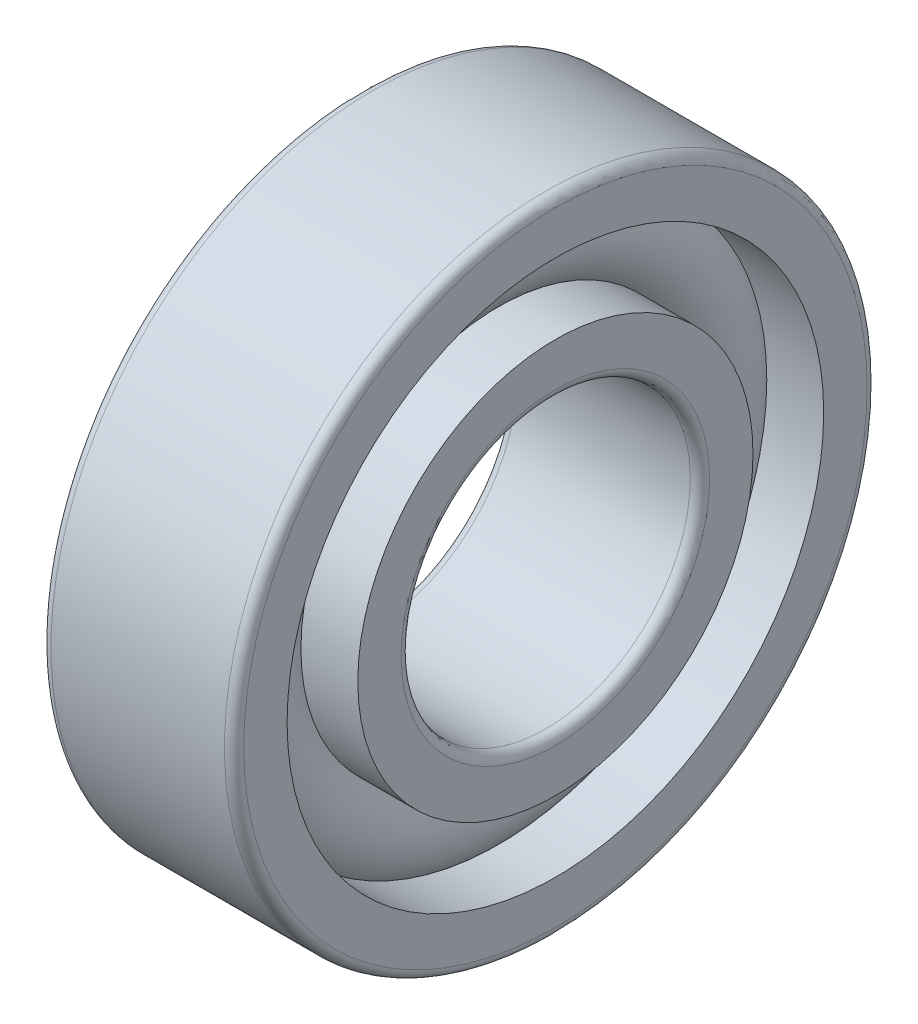
SolidWorks part; units mm, degrees
ref_plane "Plane1" through (0, 0, 0) normal (0, 0, 1) x (1, 0, 0)
ref_plane "Plane2" through (0, 0, 0) normal (0, 1, 0) x (1, 0, 0)
ref_plane "Plane3" through (0, 0, 0) normal (1, 0, 0) x (0, 0, -1)
sketch "Clipboard" plane through (0, 0, 0) normal (0, 0, 1) x (1, 0, 0)
  line L0 (-10, 0) -> (10, 0) construction
  line L1 (0, 0) -> (22.3471, -0.7804)
  line L2 (0, 0) -> (7.2456, 0.253)
  line L3 (0, 0) -> (22.3471, -0.7804)
  line L4 (0, 0) -> (-22.3573, -0.3902)
  dimension "BallCLRad" = 7.25
sketch "CagSpiSke" plane through (0, 0, 0) normal (0, 0, 1) x (1, 0, 0)
  line L0 (0.165, 6.975) -> (0.165, 7.525)
  line L1 (0.165, 7.525) -> (-0.165, 7.525)
  line L2 (-0.165, 7.525) -> (-0.165, 6.975)
  line L3 (-0.165, 6.975) -> (0.165, 6.975)
  line L4 (-20.6375, 0) -> (20.6375, 0) construction
  line L5 (0, 0) -> (0, 23.7692) construction
  dimension "OD" = 15.05
  dimension "ID" = 13.95
revolve "CageSpine" add sketch "CagSpiSke" angle 0.001 about L4
ref_axis "Axis1" through (-50, 0, 0) along (1, 0, 0)
sketch "CagBalSke" plane through (0, 0, 0) normal (0, 0, 1) x (1, 0, 0)
  line L0 (-1.815, 7.25) -> (1.815, 7.25)
  line L1 (-1.905, 7.25) -> (1.905, 7.25) construction
  line L2 (-10, 0) -> (10, 0) construction
  line L3 (0, 0) -> (0, 24) construction
  arc A0 (1.815, 7.25) -> (-1.815, 7.25) centre (0, 7.25) cw
  dimension "BallCLRad" = 7.25
revolve "CageBall" [suppressed] add sketch "CagBalSke" angle 360 about L1 reverse direction yes
pattern_circular "CageBalls" [suppressed] count 2 every 180 about axis through (-50, 0, 0) along (1, 0, 0)
sketch "CagTrmODSke" plane through (0, 0, 0) normal (0, 0, 1) x (1, 0, 0)
  line L0 (1.816, 7.525) -> (1.816, 9.066)
  line L1 (1.816, 9.066) -> (-1.816, 9.066)
  line L2 (-1.816, 9.066) -> (-1.816, 7.525)
  line L3 (-1.816, 7.525) -> (1.816, 7.525)
  line L4 (-20.6375, 0) -> (20.6375, 0) construction
  line L5 (0, 0) -> (0, 25) construction
  dimension "Width" = 3.632
  dimension "ID" = 15.05
  dimension "OD" = 18.132
revolve "CageTrimOD" [suppressed] cut sketch "CagTrmODSke" angle 360 about L4 reverse direction yes
sketch "CagTrmIDSke" plane through (0, 0, 0) normal (0, 0, 1) x (1, 0, 0)
  line L0 (1.816, 5.436) -> (1.816, 6.975)
  line L1 (1.816, 6.975) -> (-1.816, 6.975)
  line L2 (-1.816, 6.975) -> (-1.816, 5.436)
  line L3 (-1.816, 5.436) -> (1.816, 5.436)
  line L4 (-20.6375, 0) -> (20.6375, 0) construction
  line L5 (0, 0) -> (0, 25) construction
  dimension "Width" = 3.632
  dimension "ID" = 10.872
  dimension "OD" = 13.95
revolve "CageTrimID" [suppressed] cut sketch "CagTrmIDSke" angle 360 about L4 reverse direction yes
sketch "BalSimSke" plane through (0, 0, 0) normal (0, 0, 1) x (1, 0, 0)
  line L0 (-10, 0) -> (10, 0) construction
  line L1 (-10, 7.25) -> (10, 7.25) construction
  line L2 (0, 0) -> (0, 23) construction
  circle A0 centre (0, 7.25) radius 1.65
  dimension "BallCLRad" = 7.25
  dimension "Ball_diameter" = 3.3
revolve "BallsSimplified" add sketch "BalSimSke" angle 360 about L0
sketch "BalDetSke" plane through (0, 0, 0) normal (0, 0, 1) x (1, 0, 0)
  line L0 (-1.65, 7.25) -> (1.65, 7.25)
  line L1 (-1.905, 7.25) -> (1.905, 7.25) construction
  line L2 (0, 0) -> (0, 25) construction
  arc A0 (1.65, 7.25) -> (-1.65, 7.25) centre (0, 7.25) cw
  dimension "BallCLRad" = 7.25
  dimension "Ball_diameter" = 3.3
revolve "BallDetailed" [suppressed] add sketch "BalDetSke" angle 360 about L1 reverse direction yes
sketch "InnRacSke" plane through (0, 0, 0) normal (0, 0, 1) x (1, 0, 0)
  line L0 (-1.1961, 6.15) -> (-3, 6.15)
  line L1 (-3, 6.15) -> (-3, 4.8)
  line L2 (-2.7, 4.5) -> (2.7, 4.5)
  line L3 (3, 4.8) -> (3, 6.15)
  line L4 (3, 6.15) -> (1.1961, 6.15)
  line L5 (-20.6375, 0) -> (20.6375, 0) construction
  line L6 (0, 0) -> (0, 30) construction
  arc A0 (-3, 4.8) -> (-2.7, 4.5) centre (-2.7, 4.8) ccw
  arc A1 (2.7, 4.5) -> (3, 4.8) centre (2.7, 4.8) ccw
  arc A2 (1.1961, 6.15) -> (-1.1961, 6.15) centre (0, 7.25) cw
  dimension "BallCLRad" = 7.25
  dimension "Fillet_radius" = 0.3
  dimension "Ball_diameter" = 3.25
  dimension "ID" = 9
  dimension "OD" = 12.3
  dimension "Width" = 6
revolve "InnerRace" add sketch "InnRacSke" angle 360 about L5 reverse direction yes
sketch "OutRacSke" plane through (0, 0, 0) normal (0, 0, 1) x (1, 0, 0)
  line L0 (-1.1961, 8.35) -> (-3, 8.35)
  line L1 (-3, 8.35) -> (-3, 9.7)
  line L2 (-2.7, 10) -> (2.7, 10)
  line L3 (3, 9.7) -> (3, 8.35)
  line L4 (3, 8.35) -> (1.1961, 8.35)
  line L5 (-20.6375, 0) -> (20.6375, 0) construction
  line L6 (0, 0) -> (0, 30) construction
  arc A0 (-3, 9.7) -> (-2.7, 10) centre (-2.7, 9.7) cw
  arc A1 (2.7, 10) -> (3, 9.7) centre (2.7, 9.7) cw
  arc A2 (1.1961, 8.35) -> (-1.1961, 8.35) centre (0, 7.25) ccw
  dimension "BallCLRad" = 7.25
  dimension "Fillet_radius" = 0.3
  dimension "Ball_diameter" = 3.25
  dimension "Width" = 6
revolve "OuterRace" add sketch "OutRacSke" angle 360 about L5 reverse direction yes
pattern_circular "BallsDetailed" [suppressed] count 2 every 180 about axis through (-50, 0, 0) along (1, 0, 0)
equation "\"BallCLRad@Clipboard\" = ( \"OD@OutRacSke\" + \"ID@InnRacSke\" ) / 4"
equation "\"BallCLRad@BalSimSke\" = \"BallCLRad@Clipboard\""
equation "\"BallCLRad@BalDetSke\" = \"BallCLRad@Clipboard\""
equation "\"BallCLRad@InnRacSke\" = \"BallCLRad@Clipboard\""
equation "\"BallCLRad@OutRacSke\" = \"BallCLRad@Clipboard\""
equation "\"Ball_diameter@InnRacSke\" = \"Ball_diameter@BalDetSke\" - 0.05"
equation "\"Ball_diameter@OutRacSke\" = \"Ball_diameter@BalDetSke\" - 0.05"
equation "\"Ball_diameter@BalSimSke\" = \"Ball_diameter@BalDetSke\""
equation "\"Width@OutRacSke\" = \"Width@InnRacSke\""
equation "\"Fillet_radius@OutRacSke\" = \"Fillet_radius@InnRacSke\""
equation "\"Max_count@Clipboard\" = int( 3.14159265 / atn(( \"Ball_diameter@BalDetSke\" / 2) / sqr( \"BallCLRad@Clipboard\"  *  \"BallCLRad@Clipboard\" - ( \"Ball_diameter@BalDetSke\" / 2) *  ( \"Ball_diameter@BalDetSke\" / 2))))"
equation "\"Max_count@Clipboard\" = ((sgn( \"Max_count@Clipboard\" - \"Count@Clipboard\" )-1)*( \"Max_count@Clipboard\" - \"Count@Clipboard\" ))/-2+ \"Count@Clipboard\""
equation "\"Count@BallsDetailed\" = int( \"Show_count@Clipboard\" ) "
equation "\"Count@BallsDetailed\" = ((sgn( \"Count@BallsDetailed\" - \"Max_count@Clipboard\" )-1)*( \"Count@BallsDetailed\" - \"Max_count@Clipboard\" ))/-2+ \"Max_count@Clipboard\""
equation "\"Count@BallsDetailed\" = ((sgn( \"Count@BallsDetailed\" - \"Min_count@Clipboard\" )+1)*( \"Count@BallsDetailed\" - \"Min_count@Clipboard\"))/2 +\"Min_count@Clipboard\""
equation "\"Angle@BallsDetailed\" = 360.0 / \"Max_count@Clipboard\""
equation "\"BallCLRad@CagBalSke\" = \"BallCLRad@Clipboard\""
equation "\"Count@CageBalls\" = \"Count@BallsDetailed\""
equation "\"Angle@CageBalls\" = \"Angle@BallsDetailed\""
equation "\"Angle@CageSpine\" =  \"Angle@CageBalls\" * ( \"Count@CageBalls\" -1 + int( \"Count@CageBalls\" / \"Max_count@Clipboard\" ) )  + 0.001 -  int( \"Count@CageBalls\" / \"Max_count@Clipboard\" ) * 0.001"
equation "\"Angle@CageSpine\" =  \"Angle@CageSpine\" * int( \"Min_count@Clipboard\" / 2) + int(1 / \"Min_count@Clipboard\")  * 0.001"
equation "\"CageWallOD@CagBalSke\" =  \"Ball_diameter@BalDetSke\" * 1.1"
equation "\"Thickness@CagSpiSke\" =  \"Ball_diameter@BalDetSke\" * 0.1"
equation "\"OD@CagTrmODSke\" = \"BallCLRad@Clipboard\" * 2 + \"CageWallOD@CagBalSke\" + 0.002"
equation "\"ID@CagTrmODSke\" = \"BallCLRad@Clipboard\" * 2 + \"Ball_diameter@BalDetSke\" / 6"
equation "\"OD@CagTrmIDSke\" = \"BallCLRad@Clipboard\" * 2 - \"Ball_diameter@BalDetSke\" / 6"
equation "\"ID@CagTrmIDSke\" = \"BallCLRad@Clipboard\" * 2 - \"CageWallOD@CagBalSke\" + 0.002"
equation "\"OD@CagSpiSke\" = \"ID@CagTrmODSke\""
equation "\"ID@CagSpiSke\" = \"OD@CagTrmIDSke\""
equation "\"Width@CagTrmODSke\" = \"CageWallOD@CagBalSke\" + 0.002"
equation "\"Width@CagTrmIDSke\" = \"CageWallOD@CagBalSke\" + 0.002"
